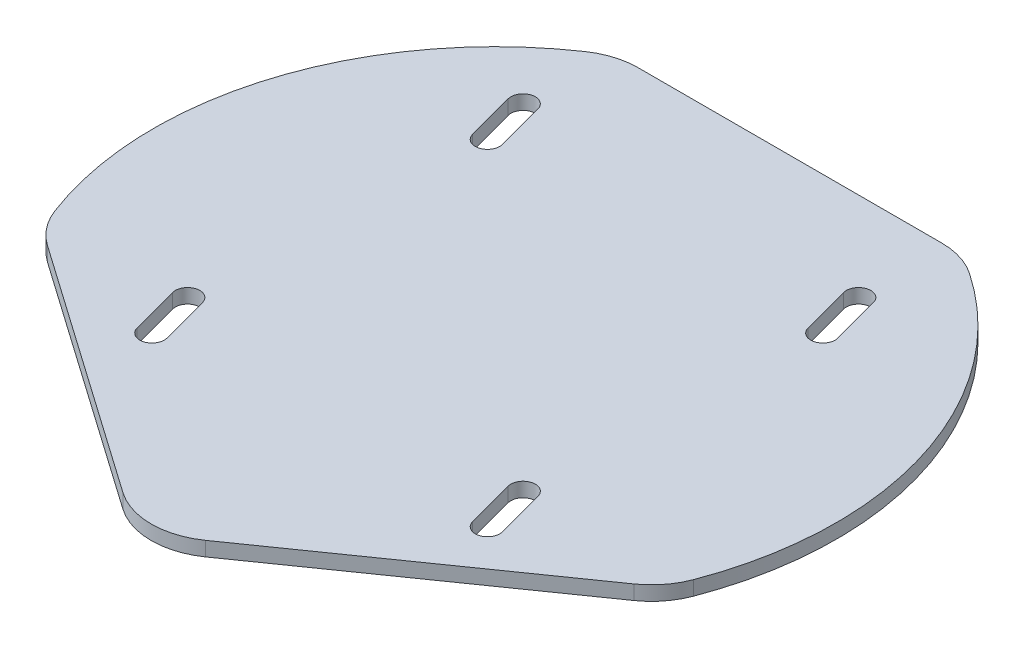
SolidWorks part; units mm, degrees
ref_plane "Plan de face" through (0, 0, 0) normal (0, 0, 1) x (1, 0, 0)
ref_plane "Plan de dessus" through (0, 0, 0) normal (0, 1, 0) x (1, 0, 0)
ref_plane "Plan de droite" through (0, 0, 0) normal (1, 0, 0) x (0, 0, -1)
sketch "Sketch1" plane through (0, 0, 0) normal (0, 1, 0) x (1, 0, 0)
  line L0 (0, 0) -> (0, 41) construction
  line L1 (0, 0) -> (-23.5166, -33.5852) construction
  line L2 (0, 0) -> (23.5166, -33.5852) construction
  line L3 (-43.1635, -19.8284) -> (0, -50.0518)
  line L4 (0, -50.0518) -> (43.1635, -19.8284)
  line L5 (-23.9844, 41) -> (23.9844, 41)
  arc A0 (-23.9844, 41) -> (-43.1635, -19.8284) centre (0, 0) ccw
  arc A1 (43.1635, -19.8284) -> (23.9844, 41) centre (0, 0) ccw
  dimension "D1" = 95
  dimension "D2" = 35
  dimension "D3" = 41
extrude "Boss-Extrude1" add sketch "Sketch1" along normal blind 2 contours L4 A0 L5 L3 region at (0, 0, -0.8358)
sketch "Esquisse1" plane through (0, 2, 0) normal (0, 1, 0) x (1, 0, 0)
  line L0 (0, 0) -> (-23.3345, 23.3345) construction
  line L1 (0, 0) -> (0, 41) construction
  line L2 (-23.9844, 41) -> (23.9844, 41) construction
  line L3 (-24.758, 28.6471) -> (-22.9463, 21.8856) construction
  line L4 (-23.116, 29.0871) -> (-21.3042, 22.3256)
  line L5 (-26.4001, 28.2071) -> (-24.5884, 21.4456)
  line L6 (0, 0) -> (23.3345, 23.3345) construction
  line L7 (0, 0) -> (23.3345, -23.3345) construction
  line L8 (0, 0) -> (-23.3345, -23.3345) construction
  line L9 (23.7228, 21.8856) -> (21.911, 28.6471) construction
  line L10 (22.0807, 21.4456) -> (20.2689, 28.2071)
  line L11 (25.3648, 22.3256) -> (23.5531, 29.0871)
  line L12 (23.7228, -24.7834) -> (21.911, -18.0219) construction
  line L13 (22.0807, -25.2234) -> (20.2689, -18.4619)
  line L14 (25.3648, -24.3434) -> (23.5531, -17.5819)
  line L15 (-22.9463, -24.7834) -> (-24.758, -18.0219) construction
  line L16 (-24.5884, -25.2234) -> (-26.4001, -18.4619)
  line L17 (-21.3042, -24.3434) -> (-23.116, -17.5819)
  line L18 (0, 0) -> (-10.9859, 41) construction
  arc A0 (-23.116, 29.0871) -> (-26.4001, 28.2071) centre (-24.758, 28.6471) ccw
  arc A1 (-24.5884, 21.4456) -> (-21.3042, 22.3256) centre (-22.9463, 21.8856) ccw
  arc A2 (22.0807, 21.4456) -> (25.3648, 22.3256) centre (23.7228, 21.8856) ccw
  arc A3 (23.5531, 29.0871) -> (20.2689, 28.2071) centre (21.911, 28.6471) ccw
  arc A4 (22.0807, -25.2234) -> (25.3648, -24.3434) centre (23.7228, -24.7834) ccw
  arc A5 (23.5531, -17.5819) -> (20.2689, -18.4619) centre (21.911, -18.0219) ccw
  arc A6 (-24.5884, -25.2234) -> (-21.3042, -24.3434) centre (-22.9463, -24.7834) ccw
  arc A7 (-23.116, -17.5819) -> (-26.4001, -18.4619) centre (-24.758, -18.0219) ccw
  point P8 (-23.8522, 25.2664)
  point P18 (22.8169, 25.2664)
  point P25 (22.8169, -21.4027)
  point P30 (-23.8522, -21.4027)
  dimension "D5" = 1.7
  dimension "D1" = 1.5
  dimension "D2" = 5.5
  dimension "D3" = 15
  dimension "D4" = 33
  dimension "D6" = 45
  dimension "D7" = 1.5
  dimension "D8" = 30
extrude "Enlèv. mat.-Extru.1" cut sketch "Esquisse1" against normal up to next
fillet "Congé1" radius 10 5 edges at (43.1635, 1, 19.8284) (23.9844, 1, -41) (-23.9844, 1, -41) (-43.1635, 1, 19.8284) (0, 1, 50.0518)
